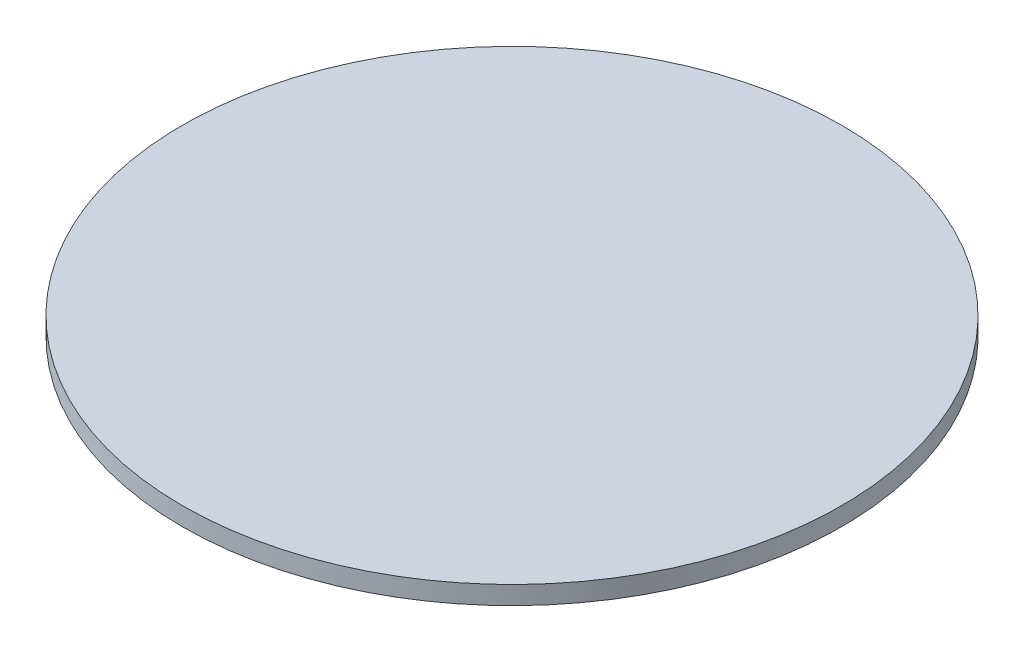
SolidWorks part; units mm, degrees
ref_plane "Plan de face" through (0, 0, 0) normal (0, 0, 1) x (1, 0, 0)
ref_plane "Plan de dessus" through (0, 0, 0) normal (0, 1, 0) x (1, 0, 0)
ref_plane "Plan de droite" through (0, 0, 0) normal (1, 0, 0) x (0, 0, -1)
sketch "Esquisse1" plane through (0, 0, 0) normal (0, 0, 1) x (1, 0, 0)
  line L4 (-22.2817, -14) -> (0, -14)
  line L5 (0, -14) -> (0, 0)
  line L6 (-22.2817, -14) -> (-22.2817, -6)
  line L7 (-22.2817, -6) -> (-23.2817, -6)
  line L8 (-23.2817, -6) -> (-23.2817, -2.5)
  line L9 (-23.2817, -2.5) -> (-45, -2.5)
  line L11 (-45, 0) -> (0, 0)
  line L12 (-45, -2.5) -> (-45, 0)
  dimension "D4" = 22.2817
  dimension "D6" = 1
  dimension "D3" = 8
  dimension "D2" = 2.5
  dimension "D5" = 14
revolve "Révolution1" add sketch "Esquisse1" angle 360 about L5
sketch "Esquisse2" plane through (0, -14, 0) normal (0, -1, 0) x (1, 0, 0)
  circle A0 centre (0, 0) radius 11.05
  dimension "D1" = 22.1
extrude "Enlèv. mat.-Extru.1" cut sketch "Esquisse2" against normal blind 8.5
sketch "Esquisse7" plane through (0, -5.5, 0) normal (0, -1, 0) x (1, 0, 0)
  circle A0 centre (0, 0) radius 9
  dimension "D1" = 18
extrude "Enlèv. mat.-Extru.5" cut sketch "Esquisse7" against normal blind 4
sketch "Esquisse10" plane through (0, -14, 0) normal (0, -1, 0) x (1, 0, 0)
  circle A0 centre (0, 0) radius 11.05 construction
  circle A1 centre (0, 0) radius 11.05
  circle A2 centre (0, 0) radius 10.85
  dimension "D1" = 0.2
extrude "Boss.-Extru.1" add sketch "Esquisse10" against normal offset from surface (0.8 mm away) 7.1 from offset 0.6 up to face at (0, -5.5, -9) offset against normal yes
sketch "Esquisse3" plane through (0, -14, 0) normal (0, -1, 0) x (1, 0, 0)
  line L0 (0, 0) -> (0, 22.2817) construction
  line L1 (0, 22.2817) -> (0.9997, 22.2593) construction
  line L2 (0.9997, 22.2593) -> (0, 0) construction
  line L3 (0.2777, 22.0276) -> (0, 22.0276)
  line L4 (0.9546, 21.256) -> (0, 21.2989) construction
  line L5 (0, 22.0276) -> (0, 22.2817)
  line L6 (1.9745, 21.939) -> (1.9973, 22.192)
  line L7 (1.6979, 21.9638) -> (1.9745, 21.939)
  arc A1 (0.2777, 22.0276) -> (0.427, 21.8633) centre (0.2777, 21.8776) cw
  arc A2 (0.427, 21.8633) -> (1.5345, 21.8136) centre (0.9795, 21.8105) ccw
  arc A3 (0, 22.2817) -> (1.9973, 22.192) centre (0, 0) cw
  arc A4 (1.6979, 21.9638) -> (1.5345, 21.8136) centre (1.6845, 21.8144) ccw
  circle A5 centre (0, 0) radius 22.2817 construction
  dimension "D2" = 0.15
  dimension "D3" = 0.555
  dimension "D5" = 0.254
  dimension "D1" = 2.571
extrude "Enlèv. mat.-Extru.4" cut sketch "Esquisse3" against normal up to surface (8 mm away) from offset 1 up to face at (0, -6, -22.2817) offset against normal yes
pattern_circular "Répétition circulaire3" count 70 over 360 about axis through (0, -14, 0) along (0, -1, 0) of "Enlèv. mat.-Extru.4"
other "Déplacer la face1" face at (0, -14, -22.2817) offset 1 parameters "D1"=1
ref_plane "Plan1" through (0, -2, 0) normal (0, -1, 0) x (-1, 0, 0)
sketch "Esquisse6" plane through (0, -6, 0) normal (0, -1, 0) x (1, 0, 0)
  circle A0 centre (0, 0) radius 22.2817 construction
  dimension "D1" = 44.5634
chamfer "Chanfrein1" distance 0.6 angle 45 2 edges at (0, -13, 23.2817) (0, -6, -23.2817)
fillet "Congé2" radius 2 1 edges at (0, -2.5, -23.2817)
sketch "Esquisse9" plane through (0, -6, 0) normal (0, -1, 0) x (1, 0, 0)
  line L140 (0.2247, 21.8276) -> (-0.2247, 21.8276)
  line L141 (2.1804, 21.7196) -> (1.7328, 21.7599)
  line L142 (4.1186, 21.4367) -> (3.6764, 21.517)
  line L143 (6.0236, 20.9812) -> (5.5903, 21.1008)
  line L144 (7.8801, 20.3568) -> (7.4593, 20.5147)
  line L145 (9.6731, 19.5685) -> (9.2682, 19.7635)
  line L146 (11.3883, 18.6227) -> (11.0025, 18.8532)
  line L147 (13.0117, 17.5268) -> (12.6482, 17.791)
  line L148 (14.5305, 16.2899) -> (14.192, 16.5856)
  line L149 (15.9322, 14.9218) -> (15.6216, 15.2467)
  line L150 (17.2056, 13.4336) -> (16.9254, 13.785)
  line L151 (18.3405, 11.8372) -> (18.093, 12.2123)
  line L152 (19.3278, 10.1456) -> (19.1148, 10.5413)
  line L153 (20.1594, 8.3722) -> (19.9828, 8.7854)
  line L154 (20.8287, 6.5314) -> (20.6899, 6.9588)
  line L155 (21.3304, 4.638) -> (21.2304, 5.0762)
  line L156 (21.6602, 2.7073) -> (21.5999, 3.1527)
  line L157 (21.8157, 0.7548) -> (21.7956, 1.2038)
  line L158 (21.7956, -1.2038) -> (21.8157, -0.7548)
  line L159 (21.5999, -3.1527) -> (21.6602, -2.7073)
  line L160 (21.2304, -5.0762) -> (21.3304, -4.638)
  line L161 (20.6899, -6.9588) -> (20.8287, -6.5314)
  line L162 (19.9828, -8.7854) -> (20.1594, -8.3722)
  line L163 (19.1148, -10.5413) -> (19.3278, -10.1456)
  line L164 (18.093, -12.2123) -> (18.3405, -11.8372)
  line L165 (16.9254, -13.785) -> (17.2056, -13.4336)
  line L166 (15.6216, -15.2467) -> (15.9322, -14.9218)
  line L167 (14.192, -16.5856) -> (14.5305, -16.2899)
  line L168 (12.6482, -17.791) -> (13.0117, -17.5268)
  line L169 (11.0025, -18.8532) -> (11.3883, -18.6227)
  line L170 (9.2682, -19.7635) -> (9.6731, -19.5685)
  line L171 (7.4593, -20.5147) -> (7.8801, -20.3568)
  line L172 (5.5903, -21.1008) -> (6.0236, -20.9812)
  line L173 (3.6764, -21.517) -> (4.1186, -21.4367)
  line L174 (1.7328, -21.7599) -> (2.1804, -21.7196)
  line L175 (-0.2247, -21.8276) -> (0.2247, -21.8276)
  line L176 (-2.1804, -21.7196) -> (-1.7328, -21.7599)
  line L177 (-4.1186, -21.4367) -> (-3.6764, -21.517)
  line L178 (-6.0236, -20.9812) -> (-5.5903, -21.1008)
  line L179 (-7.8801, -20.3568) -> (-7.4593, -20.5147)
  line L180 (-9.6731, -19.5685) -> (-9.2682, -19.7635)
  line L181 (-11.3883, -18.6227) -> (-11.0025, -18.8532)
  line L182 (-13.0117, -17.5268) -> (-12.6482, -17.791)
  line L183 (-14.5305, -16.2899) -> (-14.192, -16.5856)
  line L184 (-15.9322, -14.9218) -> (-15.6216, -15.2467)
  line L185 (-17.2056, -13.4336) -> (-16.9254, -13.785)
  line L186 (-18.3405, -11.8372) -> (-18.093, -12.2123)
  line L187 (-19.3278, -10.1456) -> (-19.1148, -10.5413)
  line L188 (-20.1594, -8.3722) -> (-19.9828, -8.7854)
  line L189 (-20.8287, -6.5314) -> (-20.6899, -6.9588)
  line L190 (-21.3304, -4.638) -> (-21.2304, -5.0762)
  line L191 (-21.6602, -2.7073) -> (-21.5999, -3.1527)
  line L192 (-21.8157, -0.7548) -> (-21.7956, -1.2038)
  line L193 (-21.7956, 1.2038) -> (-21.8157, 0.7548)
  line L194 (-21.5999, 3.1527) -> (-21.6602, 2.7073)
  line L195 (-21.2304, 5.0762) -> (-21.3304, 4.638)
  line L196 (-20.6899, 6.9588) -> (-20.8287, 6.5314)
  line L197 (-19.9828, 8.7854) -> (-20.1594, 8.3722)
  line L198 (-19.1148, 10.5413) -> (-19.3278, 10.1456)
  line L199 (-18.093, 12.2123) -> (-18.3405, 11.8372)
  line L200 (-16.9254, 13.785) -> (-17.2056, 13.4336)
  line L201 (-15.6216, 15.2467) -> (-15.9322, 14.9218)
  line L202 (-14.192, 16.5856) -> (-14.5305, 16.2899)
  line L203 (-12.6482, 17.791) -> (-13.0117, 17.5268)
  line L204 (-11.0025, 18.8532) -> (-11.3883, 18.6227)
  line L205 (-9.2682, 19.7635) -> (-9.6731, 19.5685)
  line L206 (-7.4593, 20.5147) -> (-7.8801, 20.3568)
  line L207 (-5.5903, 21.1008) -> (-6.0236, 20.9812)
  line L208 (-3.6764, 21.517) -> (-4.1186, 21.4367)
  line L209 (-1.7328, 21.7599) -> (-2.1804, 21.7196)
  line L210 (0.2247, 21.8276) -> (-0.2247, 21.8276)
  line L211 (2.1804, 21.7196) -> (1.7328, 21.7599)
  line L212 (4.1186, 21.4367) -> (3.6764, 21.517)
  line L213 (6.0236, 20.9812) -> (5.5903, 21.1008)
  line L214 (7.8801, 20.3568) -> (7.4593, 20.5147)
  line L215 (9.6731, 19.5685) -> (9.2682, 19.7635)
  line L216 (11.3883, 18.6227) -> (11.0025, 18.8532)
  line L217 (13.0117, 17.5268) -> (12.6482, 17.791)
  line L218 (14.5305, 16.2899) -> (14.192, 16.5856)
  line L219 (15.9322, 14.9218) -> (15.6216, 15.2467)
  line L220 (17.2056, 13.4336) -> (16.9254, 13.785)
  line L221 (18.3405, 11.8372) -> (18.093, 12.2123)
  line L222 (19.3278, 10.1456) -> (19.1148, 10.5413)
  line L223 (20.1594, 8.3722) -> (19.9828, 8.7854)
  line L224 (20.8287, 6.5314) -> (20.6899, 6.9588)
  line L225 (21.3304, 4.638) -> (21.2304, 5.0762)
  line L226 (21.6602, 2.7073) -> (21.5999, 3.1527)
  line L227 (21.8157, 0.7548) -> (21.7956, 1.2038)
  line L228 (21.7956, -1.2038) -> (21.8157, -0.7548)
  line L229 (21.5999, -3.1527) -> (21.6602, -2.7073)
  line L230 (21.2304, -5.0762) -> (21.3304, -4.638)
  line L231 (20.6899, -6.9588) -> (20.8287, -6.5314)
  line L232 (19.9828, -8.7854) -> (20.1594, -8.3722)
  line L233 (19.1148, -10.5413) -> (19.3278, -10.1456)
  line L234 (18.093, -12.2123) -> (18.3405, -11.8372)
  line L235 (16.9254, -13.785) -> (17.2056, -13.4336)
  line L236 (15.6216, -15.2467) -> (15.9322, -14.9218)
  line L237 (14.192, -16.5856) -> (14.5305, -16.2899)
  line L238 (12.6482, -17.791) -> (13.0117, -17.5268)
  line L239 (11.0025, -18.8532) -> (11.3883, -18.6227)
  line L240 (9.2682, -19.7635) -> (9.6731, -19.5685)
  line L241 (7.4593, -20.5147) -> (7.8801, -20.3568)
  line L242 (5.5903, -21.1008) -> (6.0236, -20.9812)
  line L243 (3.6764, -21.517) -> (4.1186, -21.4367)
  line L244 (1.7328, -21.7599) -> (2.1804, -21.7196)
  line L245 (-0.2247, -21.8276) -> (0.2247, -21.8276)
  line L246 (-2.1804, -21.7196) -> (-1.7328, -21.7599)
  line L247 (-4.1186, -21.4367) -> (-3.6764, -21.517)
  line L248 (-6.0236, -20.9812) -> (-5.5903, -21.1008)
  line L249 (-7.8801, -20.3568) -> (-7.4593, -20.5147)
  line L250 (-9.6731, -19.5685) -> (-9.2682, -19.7635)
  line L251 (-11.3883, -18.6227) -> (-11.0025, -18.8532)
  line L252 (-13.0117, -17.5268) -> (-12.6482, -17.791)
  line L253 (-14.5305, -16.2899) -> (-14.192, -16.5856)
  line L254 (-15.9322, -14.9218) -> (-15.6216, -15.2467)
  line L255 (-17.2056, -13.4336) -> (-16.9254, -13.785)
  line L256 (-18.3405, -11.8372) -> (-18.093, -12.2123)
  line L257 (-19.3278, -10.1456) -> (-19.1148, -10.5413)
  line L258 (-20.1594, -8.3722) -> (-19.9828, -8.7854)
  line L259 (-20.8287, -6.5314) -> (-20.6899, -6.9588)
  line L260 (-21.3304, -4.638) -> (-21.2304, -5.0762)
  line L261 (-21.6602, -2.7073) -> (-21.5999, -3.1527)
  line L262 (-21.8157, -0.7548) -> (-21.7956, -1.2038)
  line L263 (-21.7956, 1.2038) -> (-21.8157, 0.7548)
  line L264 (-21.5999, 3.1527) -> (-21.6602, 2.7073)
  line L265 (-21.2304, 5.0762) -> (-21.3304, 4.638)
  line L266 (-20.6899, 6.9588) -> (-20.8287, 6.5314)
  line L267 (-19.9828, 8.7854) -> (-20.1594, 8.3722)
  line L268 (-19.1148, 10.5413) -> (-19.3278, 10.1456)
  line L269 (-18.093, 12.2123) -> (-18.3405, 11.8372)
  line L270 (-16.9254, 13.785) -> (-17.2056, 13.4336)
  line L271 (-15.6216, 15.2467) -> (-15.9322, 14.9218)
  line L272 (-14.192, 16.5856) -> (-14.5305, 16.2899)
  line L273 (-12.6482, 17.791) -> (-13.0117, 17.5268)
  line L274 (-11.0025, 18.8532) -> (-11.3883, 18.6227)
  line L275 (-9.2682, 19.7635) -> (-9.6731, 19.5685)
  line L276 (-7.4593, 20.5147) -> (-7.8801, 20.3568)
  line L277 (-5.5903, 21.1008) -> (-6.0236, 20.9812)
  line L278 (-3.6764, 21.517) -> (-4.1186, 21.4367)
  line L279 (-1.7328, 21.7599) -> (-2.1804, 21.7196)
  arc A421 (0.2247, 21.8276) -> (1.7328, 21.7599) centre (0.9795, 21.8105) ccw
  arc A422 (2.1804, 21.7196) -> (3.6764, 21.517) centre (2.9306, 21.6349) ccw
  arc A423 (4.1186, 21.4367) -> (5.5903, 21.1008) centre (4.8582, 21.2851) ccw
  arc A424 (6.0236, 20.9812) -> (7.4593, 20.5147) centre (6.7466, 20.7639) ccw
  arc A425 (7.8801, 20.3568) -> (9.2682, 19.7635) centre (8.5807, 20.0755) ccw
  arc A426 (9.6731, 19.5685) -> (11.0025, 18.8532) centre (10.3457, 19.2255) ccw
  arc A427 (11.3883, 18.6227) -> (12.6482, 17.791) centre (12.0274, 18.2208) ccw
  arc A428 (13.0117, 17.5268) -> (14.192, 16.5856) centre (13.6123, 17.0693) ccw
  arc A429 (14.5305, 16.2899) -> (15.6216, 15.2467) centre (15.0876, 15.7804) ccw
  arc A430 (15.9322, 14.9218) -> (16.9254, 13.785) centre (16.4414, 14.3644) ccw
  arc A431 (17.2056, 13.4336) -> (18.093, 12.2123) centre (17.6628, 12.8328) ccw
  arc A432 (18.3405, 11.8372) -> (19.1148, 10.5413) centre (18.742, 11.1978) ccw
  arc A433 (19.3278, 10.1456) -> (19.9828, 8.7854) centre (19.6703, 9.4727) ccw
  arc A434 (20.1594, 8.3722) -> (20.6899, 6.9588) centre (20.4403, 7.6714) ccw
  arc A435 (20.8287, 6.5314) -> (21.2304, 5.0762) centre (21.0457, 5.8082) ccw
  arc A436 (21.3304, 4.638) -> (21.5999, 3.1527) centre (21.4816, 3.8983) ccw
  arc A437 (21.6602, 2.7073) -> (21.7956, 1.2038) centre (21.7445, 1.957) ccw
  arc A438 (21.8157, 0.7548) -> (21.8157, -0.7548) centre (21.8324, 0) ccw
  arc A439 (21.7956, -1.2038) -> (21.6602, -2.7073) centre (21.7445, -1.957) ccw
  arc A440 (21.5999, -3.1527) -> (21.3304, -4.638) centre (21.4816, -3.8983) ccw
  arc A441 (21.2304, -5.0762) -> (20.8287, -6.5314) centre (21.0457, -5.8082) ccw
  arc A442 (20.6899, -6.9588) -> (20.1594, -8.3722) centre (20.4403, -7.6714) ccw
  arc A443 (19.9828, -8.7854) -> (19.3278, -10.1456) centre (19.6703, -9.4727) ccw
  arc A444 (19.1148, -10.5413) -> (18.3405, -11.8372) centre (18.742, -11.1978) ccw
  arc A445 (18.093, -12.2123) -> (17.2056, -13.4336) centre (17.6628, -12.8328) ccw
  arc A446 (16.9254, -13.785) -> (15.9322, -14.9218) centre (16.4414, -14.3644) ccw
  arc A447 (15.6216, -15.2467) -> (14.5305, -16.2899) centre (15.0876, -15.7804) ccw
  arc A448 (14.192, -16.5856) -> (13.0117, -17.5268) centre (13.6123, -17.0693) ccw
  arc A449 (12.6482, -17.791) -> (11.3883, -18.6227) centre (12.0274, -18.2208) ccw
  arc A450 (11.0025, -18.8532) -> (9.6731, -19.5685) centre (10.3457, -19.2255) ccw
  arc A451 (9.2682, -19.7635) -> (7.8801, -20.3568) centre (8.5807, -20.0755) ccw
  arc A452 (7.4593, -20.5147) -> (6.0236, -20.9812) centre (6.7466, -20.7639) ccw
  arc A453 (5.5903, -21.1008) -> (4.1186, -21.4367) centre (4.8582, -21.2851) ccw
  arc A454 (3.6764, -21.517) -> (2.1804, -21.7196) centre (2.9306, -21.6349) ccw
  arc A455 (1.7328, -21.7599) -> (0.2247, -21.8276) centre (0.9795, -21.8105) ccw
  arc A456 (-0.2247, -21.8276) -> (-1.7328, -21.7599) centre (-0.9795, -21.8105) ccw
  arc A457 (-2.1804, -21.7196) -> (-3.6764, -21.517) centre (-2.9306, -21.6349) ccw
  arc A458 (-4.1186, -21.4367) -> (-5.5903, -21.1008) centre (-4.8582, -21.2851) ccw
  arc A459 (-6.0236, -20.9812) -> (-7.4593, -20.5147) centre (-6.7466, -20.7639) ccw
  arc A460 (-7.8801, -20.3568) -> (-9.2682, -19.7635) centre (-8.5807, -20.0755) ccw
  arc A461 (-9.6731, -19.5685) -> (-11.0025, -18.8532) centre (-10.3457, -19.2255) ccw
  arc A462 (-11.3883, -18.6227) -> (-12.6482, -17.791) centre (-12.0274, -18.2208) ccw
  arc A463 (-13.0117, -17.5268) -> (-14.192, -16.5856) centre (-13.6123, -17.0693) ccw
  arc A464 (-14.5305, -16.2899) -> (-15.6216, -15.2467) centre (-15.0876, -15.7804) ccw
  arc A465 (-15.9322, -14.9218) -> (-16.9254, -13.785) centre (-16.4414, -14.3644) ccw
  arc A466 (-17.2056, -13.4336) -> (-18.093, -12.2123) centre (-17.6628, -12.8328) ccw
  arc A467 (-18.3405, -11.8372) -> (-19.1148, -10.5413) centre (-18.742, -11.1978) ccw
  arc A468 (-19.3278, -10.1456) -> (-19.9828, -8.7854) centre (-19.6703, -9.4727) ccw
  arc A469 (-20.1594, -8.3722) -> (-20.6899, -6.9588) centre (-20.4403, -7.6714) ccw
  arc A470 (-20.8287, -6.5314) -> (-21.2304, -5.0762) centre (-21.0457, -5.8082) ccw
  arc A471 (-21.3304, -4.638) -> (-21.5999, -3.1527) centre (-21.4816, -3.8983) ccw
  arc A472 (-21.6602, -2.7073) -> (-21.7956, -1.2038) centre (-21.7445, -1.957) ccw
  arc A473 (-21.8157, -0.7548) -> (-21.8157, 0.7548) centre (-21.8324, 0) ccw
  arc A474 (-21.7956, 1.2038) -> (-21.6602, 2.7073) centre (-21.7445, 1.957) ccw
  arc A475 (-21.5999, 3.1527) -> (-21.3304, 4.638) centre (-21.4816, 3.8983) ccw
  arc A476 (-21.2304, 5.0762) -> (-20.8287, 6.5314) centre (-21.0457, 5.8082) ccw
  arc A477 (-20.6899, 6.9588) -> (-20.1594, 8.3722) centre (-20.4403, 7.6714) ccw
  arc A478 (-19.9828, 8.7854) -> (-19.3278, 10.1456) centre (-19.6703, 9.4727) ccw
  arc A479 (-19.1148, 10.5413) -> (-18.3405, 11.8372) centre (-18.742, 11.1978) ccw
  arc A480 (-18.093, 12.2123) -> (-17.2056, 13.4336) centre (-17.6628, 12.8328) ccw
  arc A481 (-16.9254, 13.785) -> (-15.9322, 14.9218) centre (-16.4414, 14.3644) ccw
  arc A482 (-15.6216, 15.2467) -> (-14.5305, 16.2899) centre (-15.0876, 15.7804) ccw
  arc A483 (-14.192, 16.5856) -> (-13.0117, 17.5268) centre (-13.6123, 17.0693) ccw
  arc A484 (-12.6482, 17.791) -> (-11.3883, 18.6227) centre (-12.0274, 18.2208) ccw
  arc A485 (-11.0025, 18.8532) -> (-9.6731, 19.5685) centre (-10.3457, 19.2255) ccw
  arc A486 (-9.2682, 19.7635) -> (-7.8801, 20.3568) centre (-8.5807, 20.0755) ccw
  arc A487 (-7.4593, 20.5147) -> (-6.0236, 20.9812) centre (-6.7466, 20.7639) ccw
  arc A488 (-5.5903, 21.1008) -> (-4.1186, 21.4367) centre (-4.8582, 21.2851) ccw
  arc A489 (-3.6764, 21.517) -> (-2.1804, 21.7196) centre (-2.9306, 21.6349) ccw
  arc A490 (-1.7328, 21.7599) -> (-0.2247, 21.8276) centre (-0.9795, 21.8105) ccw
  arc A491 (0.2247, 21.8276) -> (1.7328, 21.7599) centre (0.9795, 21.8105) ccw
  arc A492 (2.1804, 21.7196) -> (3.6764, 21.517) centre (2.9306, 21.6349) ccw
  arc A493 (4.1186, 21.4367) -> (5.5903, 21.1008) centre (4.8582, 21.2851) ccw
  arc A494 (6.0236, 20.9812) -> (7.4593, 20.5147) centre (6.7466, 20.7639) ccw
  arc A495 (7.8801, 20.3568) -> (9.2682, 19.7635) centre (8.5807, 20.0755) ccw
  arc A496 (9.6731, 19.5685) -> (11.0025, 18.8532) centre (10.3457, 19.2255) ccw
  arc A497 (11.3883, 18.6227) -> (12.6482, 17.791) centre (12.0274, 18.2208) ccw
  arc A498 (13.0117, 17.5268) -> (14.192, 16.5856) centre (13.6123, 17.0693) ccw
  arc A499 (14.5305, 16.2899) -> (15.6216, 15.2467) centre (15.0876, 15.7804) ccw
  arc A500 (15.9322, 14.9218) -> (16.9254, 13.785) centre (16.4414, 14.3644) ccw
  arc A501 (17.2056, 13.4336) -> (18.093, 12.2123) centre (17.6628, 12.8328) ccw
  arc A502 (18.3405, 11.8372) -> (19.1148, 10.5413) centre (18.742, 11.1978) ccw
  arc A503 (19.3278, 10.1456) -> (19.9828, 8.7854) centre (19.6703, 9.4727) ccw
  arc A504 (20.1594, 8.3722) -> (20.6899, 6.9588) centre (20.4403, 7.6714) ccw
  arc A505 (20.8287, 6.5314) -> (21.2304, 5.0762) centre (21.0457, 5.8082) ccw
  arc A506 (21.3304, 4.638) -> (21.5999, 3.1527) centre (21.4816, 3.8983) ccw
  arc A507 (21.6602, 2.7073) -> (21.7956, 1.2038) centre (21.7445, 1.957) ccw
  arc A508 (21.8157, 0.7548) -> (21.8157, -0.7548) centre (21.8324, 0) ccw
  arc A509 (21.7956, -1.2038) -> (21.6602, -2.7073) centre (21.7445, -1.957) ccw
  arc A510 (21.5999, -3.1527) -> (21.3304, -4.638) centre (21.4816, -3.8983) ccw
  arc A511 (21.2304, -5.0762) -> (20.8287, -6.5314) centre (21.0457, -5.8082) ccw
  arc A512 (20.6899, -6.9588) -> (20.1594, -8.3722) centre (20.4403, -7.6714) ccw
  arc A513 (19.9828, -8.7854) -> (19.3278, -10.1456) centre (19.6703, -9.4727) ccw
  arc A514 (19.1148, -10.5413) -> (18.3405, -11.8372) centre (18.742, -11.1978) ccw
  arc A515 (18.093, -12.2123) -> (17.2056, -13.4336) centre (17.6628, -12.8328) ccw
  arc A516 (16.9254, -13.785) -> (15.9322, -14.9218) centre (16.4414, -14.3644) ccw
  arc A517 (15.6216, -15.2467) -> (14.5305, -16.2899) centre (15.0876, -15.7804) ccw
  arc A518 (14.192, -16.5856) -> (13.0117, -17.5268) centre (13.6123, -17.0693) ccw
  arc A519 (12.6482, -17.791) -> (11.3883, -18.6227) centre (12.0274, -18.2208) ccw
  arc A520 (11.0025, -18.8532) -> (9.6731, -19.5685) centre (10.3457, -19.2255) ccw
  arc A521 (9.2682, -19.7635) -> (7.8801, -20.3568) centre (8.5807, -20.0755) ccw
  arc A522 (7.4593, -20.5147) -> (6.0236, -20.9812) centre (6.7466, -20.7639) ccw
  arc A523 (5.5903, -21.1008) -> (4.1186, -21.4367) centre (4.8582, -21.2851) ccw
  arc A524 (3.6764, -21.517) -> (2.1804, -21.7196) centre (2.9306, -21.6349) ccw
  arc A525 (1.7328, -21.7599) -> (0.2247, -21.8276) centre (0.9795, -21.8105) ccw
  arc A526 (-0.2247, -21.8276) -> (-1.7328, -21.7599) centre (-0.9795, -21.8105) ccw
  arc A527 (-2.1804, -21.7196) -> (-3.6764, -21.517) centre (-2.9306, -21.6349) ccw
  arc A528 (-4.1186, -21.4367) -> (-5.5903, -21.1008) centre (-4.8582, -21.2851) ccw
  arc A529 (-6.0236, -20.9812) -> (-7.4593, -20.5147) centre (-6.7466, -20.7639) ccw
  arc A530 (-7.8801, -20.3568) -> (-9.2682, -19.7635) centre (-8.5807, -20.0755) ccw
  arc A531 (-9.6731, -19.5685) -> (-11.0025, -18.8532) centre (-10.3457, -19.2255) ccw
  arc A532 (-11.3883, -18.6227) -> (-12.6482, -17.791) centre (-12.0274, -18.2208) ccw
  arc A533 (-13.0117, -17.5268) -> (-14.192, -16.5856) centre (-13.6123, -17.0693) ccw
  arc A534 (-14.5305, -16.2899) -> (-15.6216, -15.2467) centre (-15.0876, -15.7804) ccw
  arc A535 (-15.9322, -14.9218) -> (-16.9254, -13.785) centre (-16.4414, -14.3644) ccw
  arc A536 (-17.2056, -13.4336) -> (-18.093, -12.2123) centre (-17.6628, -12.8328) ccw
  arc A537 (-18.3405, -11.8372) -> (-19.1148, -10.5413) centre (-18.742, -11.1978) ccw
  arc A538 (-19.3278, -10.1456) -> (-19.9828, -8.7854) centre (-19.6703, -9.4727) ccw
  arc A539 (-20.1594, -8.3722) -> (-20.6899, -6.9588) centre (-20.4403, -7.6714) ccw
  arc A540 (-20.8287, -6.5314) -> (-21.2304, -5.0762) centre (-21.0457, -5.8082) ccw
  arc A541 (-21.3304, -4.638) -> (-21.5999, -3.1527) centre (-21.4816, -3.8983) ccw
  arc A542 (-21.6602, -2.7073) -> (-21.7956, -1.2038) centre (-21.7445, -1.957) ccw
  arc A543 (-21.8157, -0.7548) -> (-21.8157, 0.7548) centre (-21.8324, 0) ccw
  arc A544 (-21.7956, 1.2038) -> (-21.6602, 2.7073) centre (-21.7445, 1.957) ccw
  arc A545 (-21.5999, 3.1527) -> (-21.3304, 4.638) centre (-21.4816, 3.8983) ccw
  arc A546 (-21.2304, 5.0762) -> (-20.8287, 6.5314) centre (-21.0457, 5.8082) ccw
  arc A547 (-20.6899, 6.9588) -> (-20.1594, 8.3722) centre (-20.4403, 7.6714) ccw
  arc A548 (-19.9828, 8.7854) -> (-19.3278, 10.1456) centre (-19.6703, 9.4727) ccw
  arc A549 (-19.1148, 10.5413) -> (-18.3405, 11.8372) centre (-18.742, 11.1978) ccw
  arc A550 (-18.093, 12.2123) -> (-17.2056, 13.4336) centre (-17.6628, 12.8328) ccw
  arc A551 (-16.9254, 13.785) -> (-15.9322, 14.9218) centre (-16.4414, 14.3644) ccw
  arc A552 (-15.6216, 15.2467) -> (-14.5305, 16.2899) centre (-15.0876, 15.7804) ccw
  arc A553 (-14.192, 16.5856) -> (-13.0117, 17.5268) centre (-13.6123, 17.0693) ccw
  arc A554 (-12.6482, 17.791) -> (-11.3883, 18.6227) centre (-12.0274, 18.2208) ccw
  arc A555 (-11.0025, 18.8532) -> (-9.6731, 19.5685) centre (-10.3457, 19.2255) ccw
  arc A556 (-9.2682, 19.7635) -> (-7.8801, 20.3568) centre (-8.5807, 20.0755) ccw
  arc A557 (-7.4593, 20.5147) -> (-6.0236, 20.9812) centre (-6.7466, 20.7639) ccw
  arc A558 (-5.5903, 21.1008) -> (-4.1186, 21.4367) centre (-4.8582, 21.2851) ccw
  arc A559 (-3.6764, 21.517) -> (-2.1804, 21.7196) centre (-2.9306, 21.6349) ccw
  arc A560 (-1.7328, 21.7599) -> (-0.2247, 21.8276) centre (-0.9795, 21.8105) ccw
  dimension "D1" = 0.2
extrude "Enlèv. mat.-Extru.6" [suppressed] cut sketch "Esquisse9" along normal up to surface (7 mm away) flip side to cut up to face at (0, -13, 22.6817)
equation "\"P\"= 2"
equation "\"R1\"= 0.15"
equation "\"R2\"= 0.555"
equation "\"H\"= 0.75"
equation "\"PLD\"= 0.254"
equation "\"N\"= 70"
equation "\"D4@Esquisse1\"=\"N\"*\"P\"/PI/2"
equation "\"D2@Esquisse3\"=\"R1\""
equation "\"D3@Esquisse3\"=\"R2\""
equation "\"D5@Esquisse3\"=\"PLD\""
equation "\"D4@Esquisse3\"=\"H\"+\"PLD\""
equation "\"D1@Esquisse3\"=360/2/\"N\""
equation "\"D1@Répétition circulaire3\"=\"N\""
equation "\"D1@Esquisse6\"=\"P\"*\"N\"/PI"
